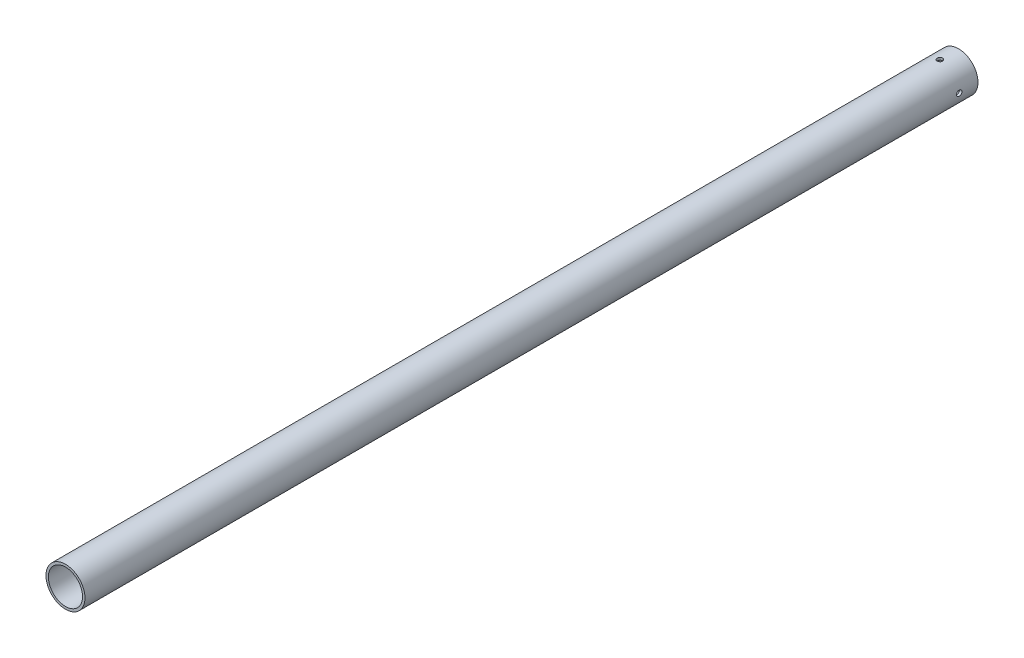
SolidWorks part; units mm, degrees
material "PC High Viscosity"
ref_plane "Front Plane" through (0, 0, 0) normal (0, 0, 1) x (1, 0, 0)
ref_plane "Top Plane" through (0, 0, 0) normal (0, 1, 0) x (1, 0, 0)
ref_plane "Right Plane" through (0, 0, 0) normal (1, 0, 0) x (0, 0, -1)
sketch "Sketch2" plane through (0, 0, 0) normal (0, 0, 1) x (1, 0, 0)
  circle A0 centre (0, 0) radius 11.1125
  circle A1 centre (0, 0) radius 12.7
  dimension "D1" = 25.4
  dimension "D2" = 22.225
extrude "Boss-Extrude1" add sketch "Sketch2" along normal mid plane 581.2193
sketch "Sketch3" plane through (0, 0, 0) normal (0, 1, 0) x (1, 0, 0)
  line L0 (12.7, 290.6096) -> (-12.7, 290.6096) construction
  circle A0 centre (0, 278.4176) radius 1.7526
  dimension "D1" = 3.5052
  dimension "D2" = 12.192
extrude "Cut-Extrude1" cut sketch "Sketch3" against normal through all both and the other way through all
sketch "Sketch5" plane through (0, 0, 0) normal (1, 0, 0) x (0, 0, -1)
  line L0 (290.6096, -12.7) -> (290.6096, 12.7) construction
  circle A0 centre (278.4176, 0) radius 1.7526
  dimension "D1" = 3.5052
  dimension "D2" = 12.192
extrude "Cut-Extrude2" cut sketch "Sketch5" against normal through all both and the other way through all
